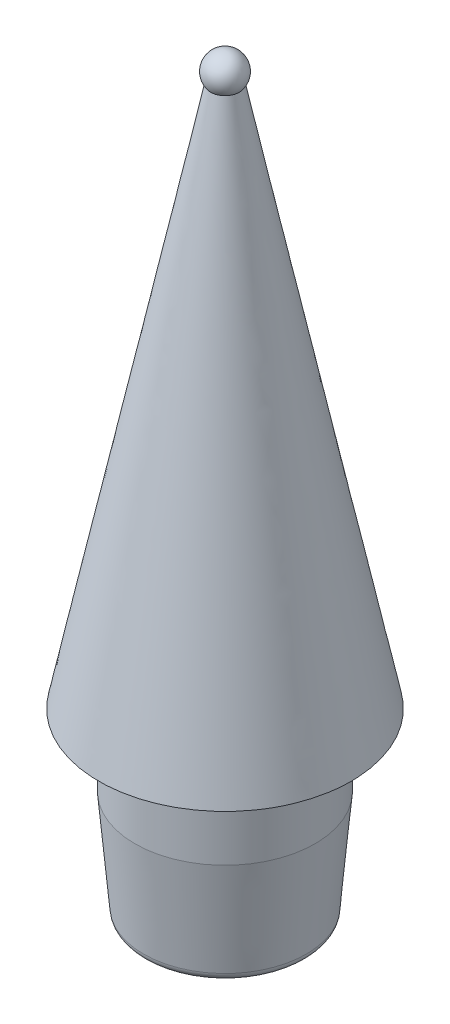
SolidWorks part; units mm, degrees
material "ABS"
ref_plane "Front Plane" through (0, 0, 0) normal (0, 0, 1) x (1, 0, 0)
ref_plane "Top Plane" through (0, 0, 0) normal (0, 1, 0) x (1, 0, 0)
ref_plane "Right Plane" through (0, 0, 0) normal (1, 0, 0) x (0, 0, -1)
sketch "Sketch1" plane through (0, 0, 0) normal (0, 1, 0) x (1, 0, 0)
  circle A0 centre (0, 0) radius 2.5
  dimension "D1" = 5
extrude "Boss-Extrude1" add sketch "Sketch1" along normal blind 5
sketch "Sketch2" plane through (0, 5, 0) normal (0, 1, 0) x (1, 0, 0)
  circle A0 centre (0, 0) radius 3.5
  dimension "D1" = 7
ref_plane "Plane1" through (0, 20, 0) normal (0, 1, 0) x (1, 0, 0)
sketch "Sketch3" plane through (0, 20, 0) normal (0, 1, 0) x (1, 0, 0)
  circle A0 centre (0, 0) radius 0.4
  circle A1 centre (0, 0) radius 0.5 construction
  circle A2 centre (0, 0) radius 0.5 construction
  point P5 (0.898, 0.638)
  point P6 (0.898, 0.638)
  dimension "D1" = 0.1
  dimension "D3" = 1
loft "Loft1" add profiles "Sketch3", "Sketch2" connector at (-0.3536, 20, -0.187) connector at (-3.3635, 5, -0.968)
sketch "Sketch4" plane through (0, 0, 0) normal (0, 1, 0) x (1, 0, 0)
  circle A0 centre (0, 0) radius 1.075
  dimension "D1" = 2.15
extrude "Cut-Extrude1" cut sketch "Sketch4" along normal blind 13 contours A0
chamfer "Chamfer1" distance 0.3 angle 88 1 edges at (0, 0, 1.075) first distance on face at (0, 0, 1.075)
chamfer "Chamfer2" distance 3 angle 5 1 edges at (0, 0, 2.5) first distance on face at (0, 5, 2.5)
fillet "Fillet2" radius 0.25 1 edges at (0, 5, 2.5)
fillet "Fillet4" radius 0.25 2 edges at (0, 0, 1.375) (0, 0, 2.2375)
sketch "Sketch5" plane through (0, 0, 0) normal (0, 0, 1) x (1, 0, 0)
  line L0 (0, 24.7272) -> (0, 0) construction
  line L1 (0, 20.8) -> (0, 19.8)
  line L2 (0.4, 20) -> (-0.4, 20) construction
  line L3 (0.4, 20) -> (-0.4, 20) construction
  arc A0 (0, 20.8) -> (0, 19.8) centre (0, 20.3) ccw
  dimension "D1" = 0.5
revolve "Revolve1" add sketch "Sketch5" angle 360 about L0
sketch "Sketch6" plane through (0, 13, 0) normal (0, -1, 0) x (1, 0, 0)
  circle A0 centre (0, 0) radius 0.55
  dimension "D1" = 1.1
extrude "Cut-Extrude2" cut sketch "Sketch6" against normal blind 4 contours A0
fillet "Fillet5" radius 0.1 1 edges at (0, 13, -0.55)
